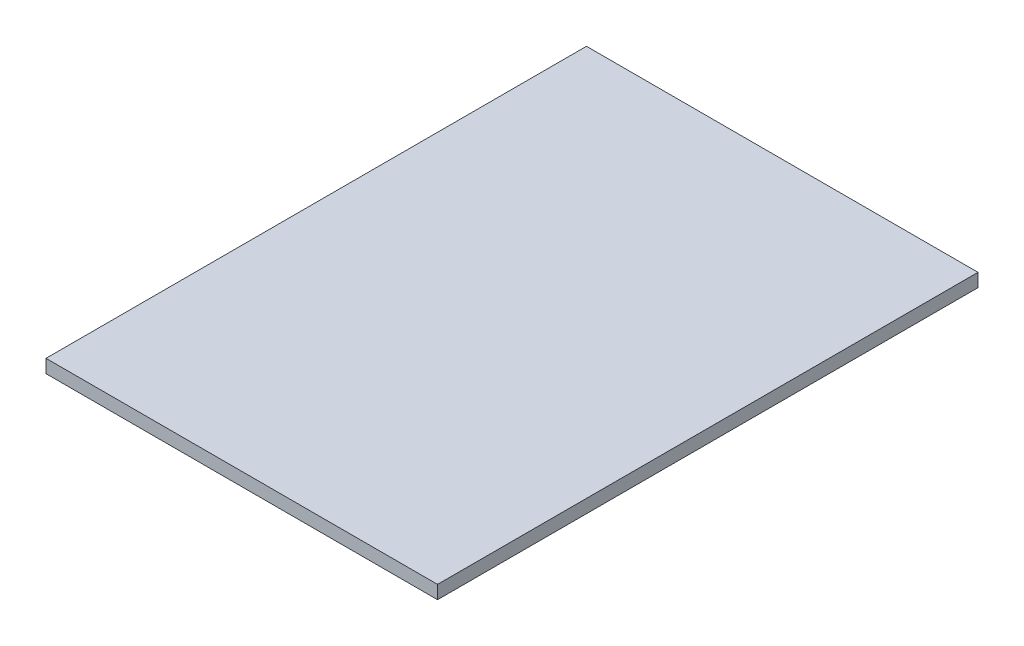
SolidWorks part; units mm, degrees
ref_plane "Front Plane" through (0, 0, 0) normal (0, 0, 1) x (1, 0, 0)
ref_plane "Top Plane" through (0, 0, 0) normal (0, 1, 0) x (1, 0, 0)
ref_plane "Right Plane" through (0, 0, 0) normal (1, 0, 0) x (0, 0, -1)
sketch "Sketch1" plane through (0, 0, 0) normal (0, 1, 0) x (1, 0, 0)
  line L1 (0, 0) -> (467.36, 0)
  line L2 (0, 0) -> (0, 645.16)
  line L3 (0, 645.16) -> (467.36, 645.16)
  line L4 (467.36, 0) -> (467.36, 645.16)
  dimension "D1" = 467.36
  dimension "D2" = 645.16
extrude "Boss-Extrude1" add sketch "Sketch1" along normal blind 15.875
